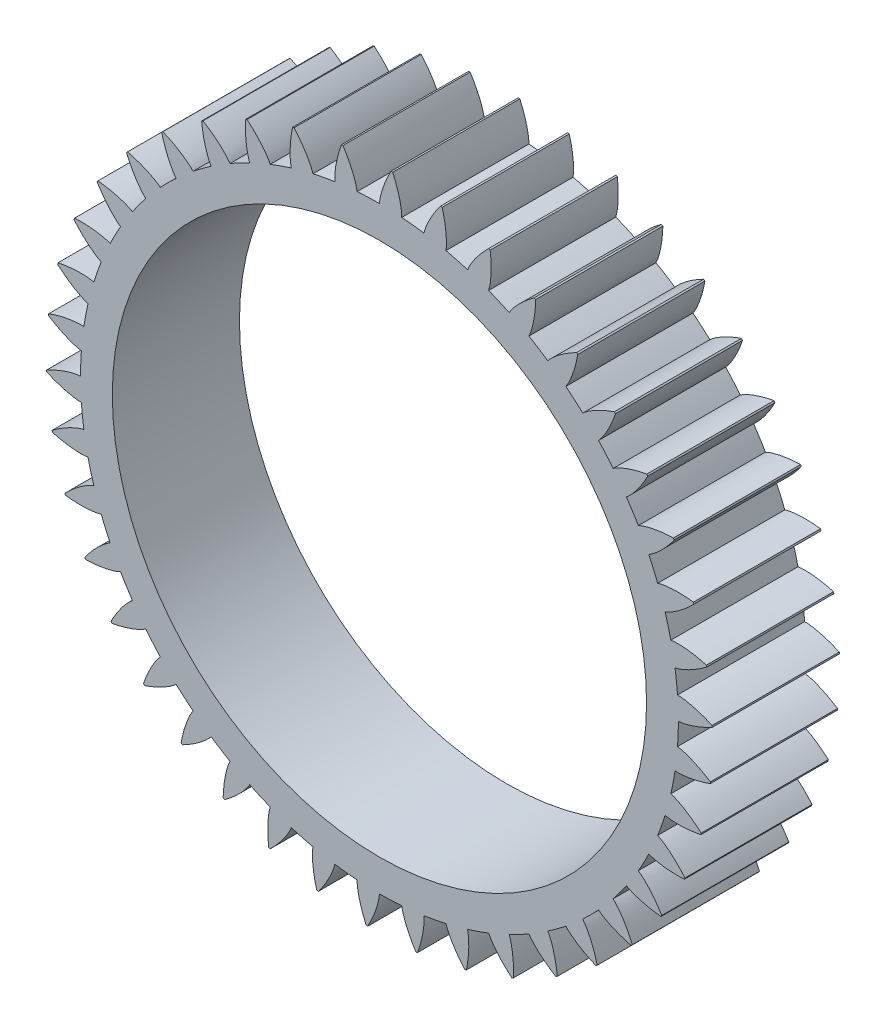
SolidWorks part; units mm, degrees
ref_plane "Front Plane" through (0, 0, 0) normal (0, 0, 1) x (1, 0, 0)
ref_plane "Top Plane" through (0, 0, 0) normal (0, 1, 0) x (1, 0, 0)
ref_plane "Right Plane" through (0, 0, 0) normal (1, 0, 0) x (0, 0, -1)
sketch "Sketch1" plane through (0, 0, 0) normal (0, 0, 1) x (1, 0, 0)
  line L0 (0, 0) -> (52.3443, -1.9586) construction
  line L1 (0, 0) -> (52.3443, 1.9586) construction
  line L2 (0, 0) -> (52.3443, -1.9586) construction
  line L3 (0, 0) -> (52.381, 0) construction
  line L4 (0, 0) -> (52.0516, 5.8648) construction
  line L5 (46.9846, 0) -> (47.0238, 0)
  line L6 (52.3443, 1.9586) -> (41.9944, 1.5713)
  line L7 (46.9909, -1.7583) -> (41.9944, -1.5713)
  circle A0 centre (0, 0) radius 50 construction
  circle A1 centre (0, 0) radius 47.0238 construction
  circle A2 centre (0, 0) radius 46.9846 construction
  circle A3 centre (0, 0) radius 52.381 construction
  arc A4 (47.0238, 0) -> (46.9909, -1.7583) centre (0, 0) cw
  arc A5 (41.9944, -1.5713) -> (41.9944, 1.5713) centre (0, 0) ccw
  arc A6 (52.349, 1.8297) -> (52.3443, 1.9586) centre (0, 0) ccw
  spline S0 degree 4 poles (46.9846, 0) (47.0542, 0.0021) (47.2491, 0.0144) (47.6157, 0.0631) (48.2083, 0.1783) (48.9529, 0.3772) (49.8992, 0.6933) (50.9896, 1.14) (52.1576, 1.7073) (53.3908, 2.4042) (54.5846, 3.1689) (55.7382, 3.9931) (56.8519, 4.8701) (58.1554, 5.9924) (59.6542, 7.4275) (61.3023, 9.2133) (63.0466, 11.3838) (64.6758, 13.7052) (66.1606, 16.1214) (67.3362, 18.3064) (68.2574, 20.2229) (68.9684, 21.8454) (69.5036, 23.1582) (70.1308, 24.814) (70.7037, 26.4925) (71.222, 28.1838) (71.6883, 29.8972) (72.0283, 31.2655) (72.3017, 32.4889) (72.5117, 33.5083) (72.6824, 34.4144) (72.796, 35.0421) (72.9279, 35.838) (73.0061, 36.3352) (73.1112, 37.0425) (73.1843, 37.5766) (73.2643, 38.188) (73.3323, 38.7556) (73.3995, 39.3508) (73.4589, 39.929) (73.5013, 40.373) (73.5271, 40.6641) (73.5398, 40.811) knots 0 0 0 0 0 0.005377 0.015084 0.028532 0.04661 0.064855 0.092111 0.119476 0.146842 0.174209 0.201575 0.228941 0.256307 0.307035 0.361767 0.4165 0.471232 0.525964 0.580697 0.608063 0.635429 0.662795 0.690161 0.744894 0.77226 0.799626 0.826992 0.854358 0.868042 0.881725 0.895408 0.909091 0.920455 0.931818 0.943182 0.954545 0.965909 0.977273 0.988636 1 1 1 1 1 construction
  spline S1 degree 4 poles (46.9846, 0) (47.0542, 0.0021) (47.2491, 0.0144) (47.6157, 0.0631) (48.2083, 0.1783) (48.9529, 0.3772) (49.8992, 0.6933) (50.9896, 1.14) (52.1576, 1.7073) (53.3908, 2.4042) (54.5846, 3.1689) (55.7382, 3.9931) (56.8519, 4.8701) (58.1554, 5.9924) (59.6542, 7.4275) (61.3023, 9.2133) (63.0466, 11.3838) (64.6758, 13.7052) (66.1606, 16.1214) (67.3362, 18.3064) (68.2574, 20.2229) (68.9684, 21.8454) (69.5036, 23.1582) (70.1308, 24.814) (70.7037, 26.4925) (71.222, 28.1838) (71.6883, 29.8972) (72.0283, 31.2655) (72.3017, 32.4889) (72.5117, 33.5083) (72.6824, 34.4144) (72.796, 35.0421) (72.8993, 35.6655) (72.9497, 35.9793) (72.9746, 36.1384) knots 0 0 0 0 0 0.005377 0.015084 0.028532 0.04661 0.064855 0.092111 0.119476 0.146842 0.174209 0.201575 0.228941 0.256307 0.307035 0.361767 0.4165 0.471232 0.525964 0.580697 0.608063 0.635429 0.662795 0.690161 0.744894 0.77226 0.799626 0.826992 0.854358 0.868042 0.881725 0.895408 0.909091 0.909091 0.909091 0.909091 0.909091
  point P6 (46.9846, 0)
  dimension "pitchRadius" = 50
  dimension "addendumRadius" = 52.381
  dimension "dedendumRadius" = 47.0238
  dimension "baseRadius" = 46.9846
  dimension "D1" = 4.286
  dimension "D2" = 2.143
  dimension "toothArc" = 8.571
  dimension "D3" = 5
extrude "Boss-Extrude1" add sketch "Sketch1" along normal blind 20 contours S1 | S1 region at (45.7543, 0.3105, 0)
mirror "Mirror1" about plane through (0, 0, 20) normal (0.0374, -0.9993, 0) of "Boss-Extrude1"
pattern_circular "CirPattern2" count 42 over 360 about axis through (0, 0, 20) along (0, 0, -1) of "Boss-Extrude1", "Mirror1"
ref_axis "Axis1" through (0, 0, 0) along (0, 0, 1)
equation "\"D2@Sketch1\"=\"toothArc@Sketch1\"/4"
equation "\"pitchRadius\"= 5"
equation "\"nTeeth\"= 42"
equation "\"pressureAngle\"= 20"
equation "\"baseRadius\"= \"pitchRadius\" * cos ( \"pressureAngle\" )"
equation "\"diametralPitch\"= \"nTeeth\" / ( 2 * \"pitchRadius\" )'note units: cm^-1"
equation "\"dedendum\"= 1.25 / \"diametralPitch\"'for full depth, 20 deg pressure angle"
equation "\"addendum\"= 1 / \"diametralPitch\""
equation "\"pitchRadius@Sketch1\"= \"pitchRadius\""
equation "\"addendumRadius@Sketch1\"= \"pitchRadius\" + \"addendum\""
equation "\"dedendumRadius@Sketch1\"= \"pitchRadius\" - \"dedendum\""
equation "\"baseRadius@Sketch1\"= \"baseRadius\""
equation "\"toothArc@Sketch1\"=360/\"nTeeth\""
equation "\"D2@CirPattern2\"=\"nTeeth\""
equation "\"D1@CirPattern2\"= \"nTeeth\""
equation "\"D1@Sketch1\"=\"toothArc@Sketch1\"/2"
